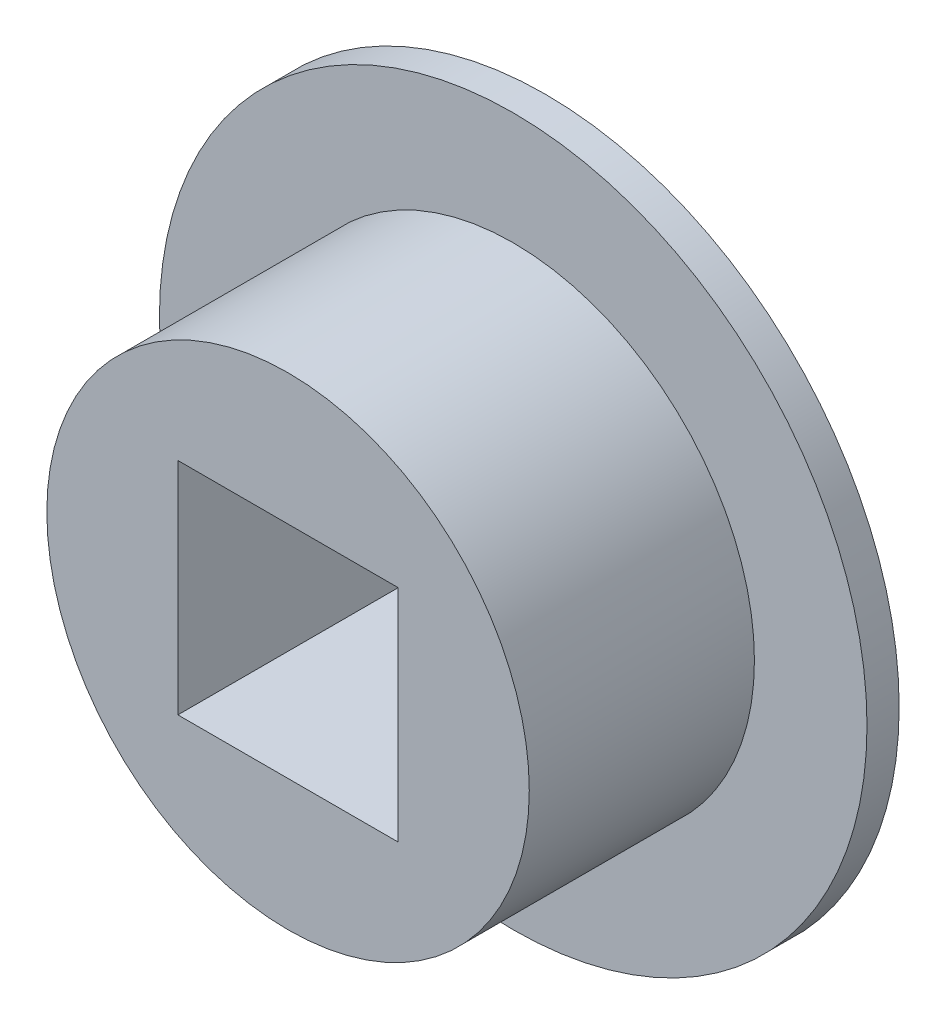
SolidWorks part; units mm, degrees
ref_plane "Front Plane" through (0, 0, 0) normal (0, 0, 1) x (1, 0, 0)
ref_plane "Top Plane" through (0, 0, 0) normal (0, 1, 0) x (1, 0, 0)
ref_plane "Right Plane" through (0, 0, 0) normal (1, 0, 0) x (0, 0, -1)
sketch "Sketch1" plane through (0, 0, 0) normal (0, 0, 1) x (1, 0, 0)
  line L1 (-3.425, -3.425) -> (3.425, -3.425)
  line L2 (-3.425, -3.425) -> (-3.425, 3.425)
  line L3 (-3.425, 3.425) -> (3.425, 3.425)
  line L4 (3.425, -3.425) -> (3.425, 3.425)
  line L5 (-3.425, -3.425) -> (3.425, 3.425) construction
  line L6 (-3.425, 3.425) -> (3.425, -3.425) construction
  circle A0 centre (0, 0) radius 7.5
  point P0 (0, 0)
  point P9 (0, 0)
  dimension "D2" = 15
  dimension "D1" = 6.85
extrude "Boss-Extrude1" add sketch "Sketch1" along normal mid plane 8
ref_axis "Axis1" through (0, 0, 0) along (0, 0, 1)
sketch "Sketch2" plane through (0, 0, -4) normal (0, 0, -1) x (-1, 0, 0)
  circle A0 centre (0, 0) radius 11
  circle A1 centre (0, 0) radius 7.5
  circle A2 centre (0, 0) radius 7.5 construction
  dimension "D1" = 3.5
extrude "Boss-Extrude2" add sketch "Sketch2" against normal blind 1
